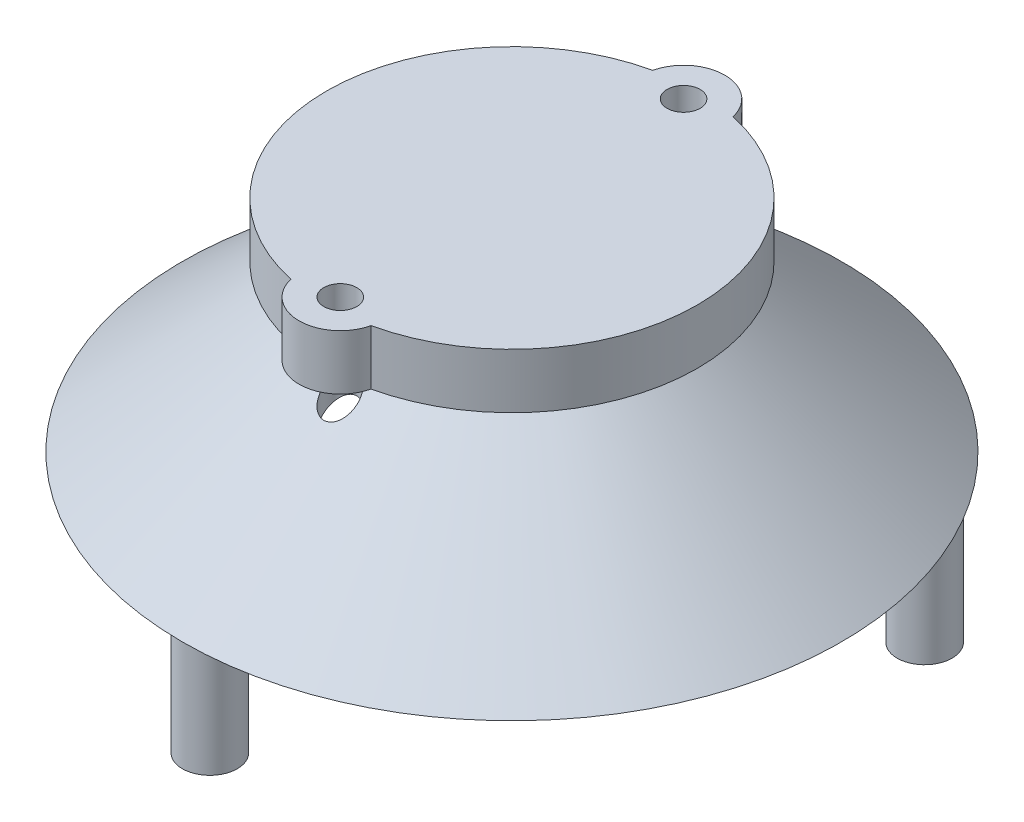
SolidWorks part; units mm, degrees
ref_plane "Front Plane" through (0, 0, 0) normal (0, 0, 1) x (1, 0, 0)
ref_plane "Top Plane" through (0, 0, 0) normal (0, 1, 0) x (1, 0, 0)
ref_plane "Right Plane" through (0, 0, 0) normal (1, 0, 0) x (0, 0, -1)
ref_axis "Center Axis" through (0, 0.65, 0) along (0, -1, 0)
sketch "STR Point" plane through (0, 0, 0) normal (0, 1, 0) x (1, 0, 0)
  point P0 (0.8, 2.9)
  dimension "D1" = 0.8
  dimension "D2" = 2.9
ref_axis "STR Axis" through (0.8, 0, -2.9) along (0, 1, 0)
ref_plane "Plane1" through (0, -10, 0) normal (0, 1, 0) x (1, 0, 0)
sketch "Sketch1" plane through (0, 0, 0) normal (0, 1, 0) x (1, 0, 0)
  arc A0 (1.461, -6.59) -> (1.461, 6.59) centre (0, 0) ccw
  arc A1 (1.461, 6.59) -> (-1.461, 6.59) centre (0, 6.25) ccw
  arc A2 (-1.461, -6.59) -> (1.461, -6.59) centre (0, -6.25) ccw
  arc A3 (-1.461, 6.59) -> (-1.461, -6.59) centre (0, 0) ccw
  dimension "D1" = 6.25
  dimension "D2" = 6.25
extrude "Boss-Extrude4" add sketch "Sketch1" along normal blind 2 separate body
sketch "Sketch3" plane through (0, 0, 0) normal (1, 0, 0) x (0, 0, -1)
  line L0 (-4, 0) -> (-5, 0)
  line L1 (-6.59, 0) -> (6.59, 0) construction
  line L2 (-5, 0) -> (-12, -6)
  line L3 (-12, -6) -> (-11, -6)
  line L4 (-11, -6) -> (-4, 0)
  dimension "D1" = 1
  dimension "D2" = 6
  dimension "D3" = 12
  dimension "D4" = 5
revolve "Revolve1" add sketch "Sketch3" angle 360 about axis through (0, 0.65, 0) along (0, -1, 0)
sketch "Peg" plane through (0, -10, 0) normal (0, 1, 0) x (1, 0, 0)
  circle A0 centre (0, -11) radius 1
  circle A1 centre (-9.5263, 5.5) radius 1
  circle A2 centre (9.5263, 5.5) radius 1
  point P10 (0, 0)
  dimension "D1" = 11
  dimension "D2" = 3
extrude "Boss-Extrude3" add sketch "Peg" along normal up to next
sketch "Sketch4" plane through (0, 2, 0) normal (0, 1, 0) x (1, 0, 0)
  circle A0 centre (0, 6.25) radius 0.6
  circle A1 centre (0, -6.25) radius 0.6
extrude "Cut-Extrude1" cut sketch "Sketch4" against normal through all
